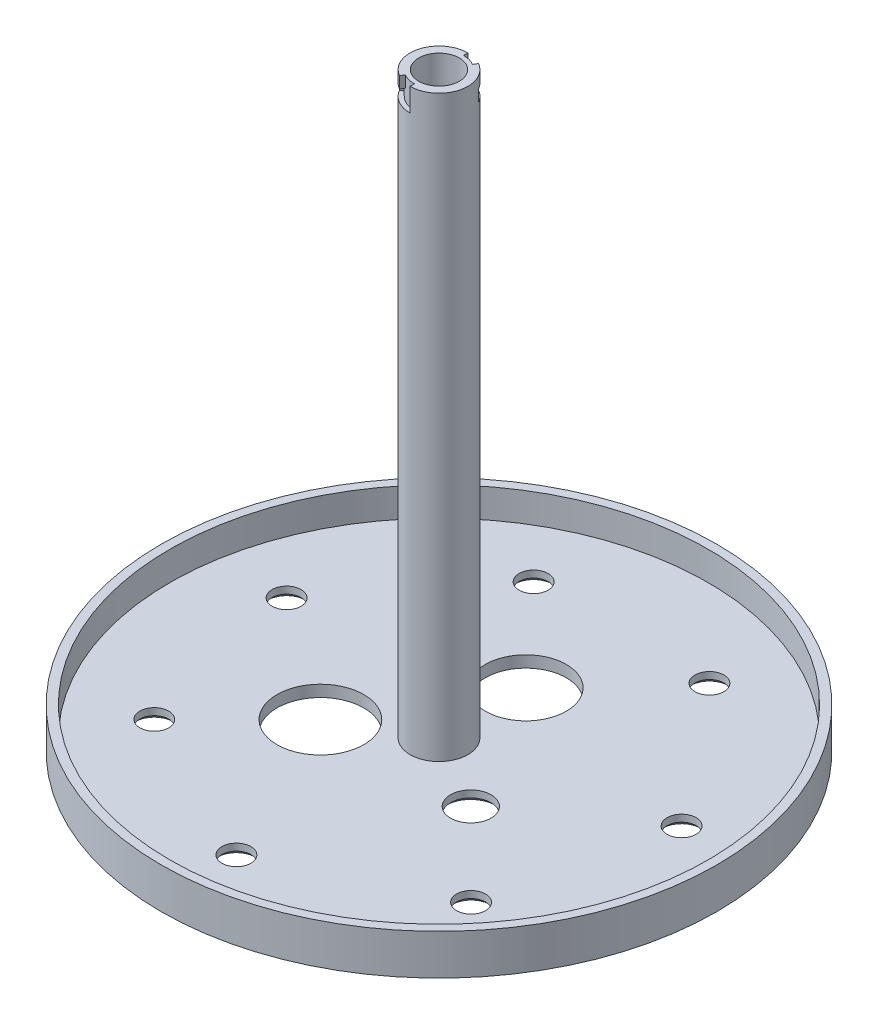
SolidWorks part; units mm, degrees
ref_plane "Front Plane" through (0, 0, 0) normal (0, 0, 1) x (1, 0, 0)
ref_plane "Top Plane" through (0, 0, 0) normal (0, 1, 0) x (1, 0, 0)
ref_plane "Right Plane" through (0, 0, 0) normal (1, 0, 0) x (0, 0, -1)
sketch "Sketch1" plane through (0, 0, 0) normal (0, 1, 0) x (1, 0, 0)
  line L0 (0, 15) -> (0, 0) construction
  line L1 (0, 0) -> (-12.9904, -7.5) construction
  line L2 (0, 0) -> (12.9904, -7.5) construction
  circle A0 centre (0, 0) radius 46.5
  circle A1 centre (0, 15) radius 7
  circle A2 centre (-12.9904, -7.5) radius 7.5
  circle A3 centre (12.9904, -7.5) radius 3.5
  circle A4 centre (0, 0) radius 3.5
  point P3 (0, 15)
  point P8 (12.9904, -7.5)
  point P9 (-12.9904, -7.5)
  point P10 (0, 0)
  dimension "D1" = 93
  dimension "D4" = 14
  dimension "D5" = 15
  dimension "D6" = 7
  dimension "D7" = 7
  dimension "D2" = 15
  dimension "D3" = 3
extrude "Boss-Extrude1" add sketch "Sketch1" along normal blind 2
sketch "Sketch2" plane through (0, 2, 0) normal (0, 1, 0) x (1, 0, 0)
  line L0 (0, 0) -> (12.9904, -7.5) construction
  line L1 (0, 0) -> (0, 46.5) construction
  line L2 (0, 0) -> (-12.9904, -7.5) construction
  line L3 (0, 0) -> (-40.2702, -23.25) construction
  line L4 (0, 0) -> (40.2702, -23.25) construction
  circle A0 centre (0, 0) radius 46.5 construction
  circle A1 centre (-12.9904, -7.5) radius 7.5 construction
  circle A2 centre (12.9904, -7.5) radius 3.5 construction
  circle A3 centre (0, 0) radius 25
  circle A4 centre (21.6506, -12.5) radius 3
  circle A5 centre (-21.6506, -12.5) radius 3
  circle A6 centre (0, 25) radius 3
  point P22 (0, 0)
  dimension "D1" = 50
  dimension "D2" = 6
  dimension "D3" = 3
ref_plane "Plane1" through (0, 0, 0) normal (-0.5, 0, -0.866) x (-0.866, 0, 0.5)
sketch "Sketch3" plane through (0, 2, 0) normal (0, 1, 0) x (1, 0, 0)
  circle A0 centre (0, 0) radius 3.5
  circle A1 centre (0, 0) radius 5
  dimension "D1" = 10
extrude "Boss-Extrude2" add sketch "Sketch3" along normal blind 100
sketch "Sketch6" plane through (0, 0, 0) normal (0, -1, 0) x (1, 0, 0)
  circle A0 centre (0, 0) radius 35
  circle A1 centre (0, 35) radius 2.5
  circle A2 centre (27.3641, 21.8221) radius 2.5
  circle A3 centre (34.1225, -7.7882) radius 2.5
  circle A4 centre (15.1859, -31.5339) radius 2.5
  circle A5 centre (-15.1859, -31.5339) radius 2.5
  circle A6 centre (-34.1225, -7.7882) radius 2.5
  circle A7 centre (-27.3641, 21.8221) radius 2.5
  point P20 (0, 0)
  dimension "D1" = 70
  dimension "D2" = 5
  dimension "D3" = 7
extrude "Cut-Extrude2" cut sketch "Sketch6" against normal up to next contours A0 A4 | A0 A4 | A0 A3 | A0 A3 | A0 A2 | A0 A2 | A0 A1 | A0 A1 | A0 A7 | A0 A7 | A0 A6 | A0 A6 | A0 A5 | A0 A5 region at (26.5221, 0, 21.1507) region at (28.181, 0, 22.4736) region at (35.1411, 0, -8.0207) region at (33.0725, 0, -7.5486) region at (0, 0, 33.923) region at (0, 0, 36.0448) region at (15.6392, 0, -32.4752) region at (14.7187, 0, -30.5636) region at (-26.5221, 0, 21.1507) region at (-28.181, 0, 22.4736) region at (-15.6392, 0, -32.4752) region at (-14.7187, 0, -30.5636) region at (-33.0725, 0, -7.5486) region at (-35.1411, 0, -8.0207)
chamfer "Chamfer2" distance 0.8 angle 45 8 edges at (0, 0, 32.5) (-27.3641, 0, 19.3221) (-34.1225, 0, -10.2882) (-15.1859, 0, -34.0339) (27.3641, 0, 19.3221) (12.9904, 0, 11) (34.1225, 0, -10.2882) (15.1859, 0, -34.0339)
ref_axis "Axis1" through (0, 102, 0) along (0, -1, 0)
sketch "Sketch7" plane through (0, 0, 0) normal (1, 0, 0) x (0, 0, -1)
  line L1 (5, 102) -> (4.25, 102)
  line L2 (5, 102) -> (5, 100)
  line L3 (5, 100) -> (4.25, 100)
  line L4 (4.25, 102) -> (4.25, 100)
  line L5 (5, 100) -> (4.25, 100)
  line L6 (5, 100) -> (5, 98)
  line L7 (5, 98) -> (4.25, 98)
  line L8 (4.25, 100) -> (4.25, 98)
  dimension "D1" = 2
  dimension "D2" = 0.75
  dimension "D3" = 2
  dimension "D4" = 0.75
revolve "Cut-Revolve1" cut sketch "Sketch7" angle 30 about axis through (0, 102, 0) along (0, -1, 0) region at (0, 101, -4.625)
revolve "Cut-Revolve2" cut sketch "Sketch7<4>" angle 60 about axis through (0, 102, 0) along (0, -1, 0) region at (0, 99, -4.625)
sketch "Sketch7<4>" plane through (0, 0, 0) normal (1, 0, 0) x (0, 0, -1) same geometry as "Sketch7"
pattern_circular "CirPattern5" count 2 over 360 about axis through (0, 102, 0) along (0, -1, 0) of "Cut-Revolve2", "Cut-Revolve1"
sketch "Sketch8" plane through (0, 2, 0) normal (0, 1, 0) x (1, 0, 0)
  circle A0 centre (0, 0) radius 48
  circle A1 centre (0, 0) radius 46.5
  dimension "D1" = 96
extrude "Boss-Extrude3" add sketch "Sketch8" along normal blind 5 and the other way blind 2 separate body
